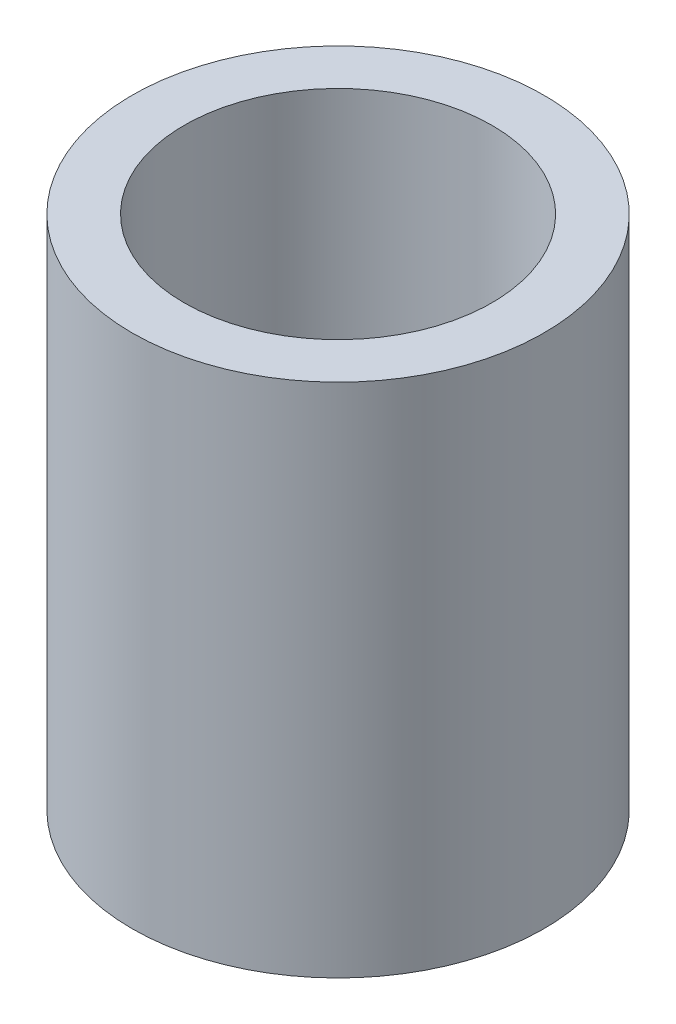
SolidWorks part; units mm, degrees
ref_plane "Front Plane" through (0, 0, 0) normal (0, 0, 1) x (1, 0, 0)
ref_plane "Top Plane" through (0, 0, 0) normal (0, 1, 0) x (1, 0, 0)
ref_plane "Right Plane" through (0, 0, 0) normal (1, 0, 0) x (0, 0, -1)
sketch "Sketch1" plane through (0, 0, 0) normal (0, 1, 0) x (1, 0, 0)
  circle A0 centre (0, 0) radius 15
  dimension "SLEEVE_OD" = 30
extrude "Boss-Extrude1" add sketch "Sketch1" along normal blind 37.5883
sketch "Sketch2" plane through (0, 0, 0) normal (0, 1, 0) x (1, 0, 0)
  circle A0 centre (0, 0) radius 11.207
  dimension "BORE_D" = 22.4139
extrude "Cut-Extrude1" cut sketch "Sketch2" along normal through all
chamfer "Chamfer1" distance 2.8373 angle 45 rebuild error yes
